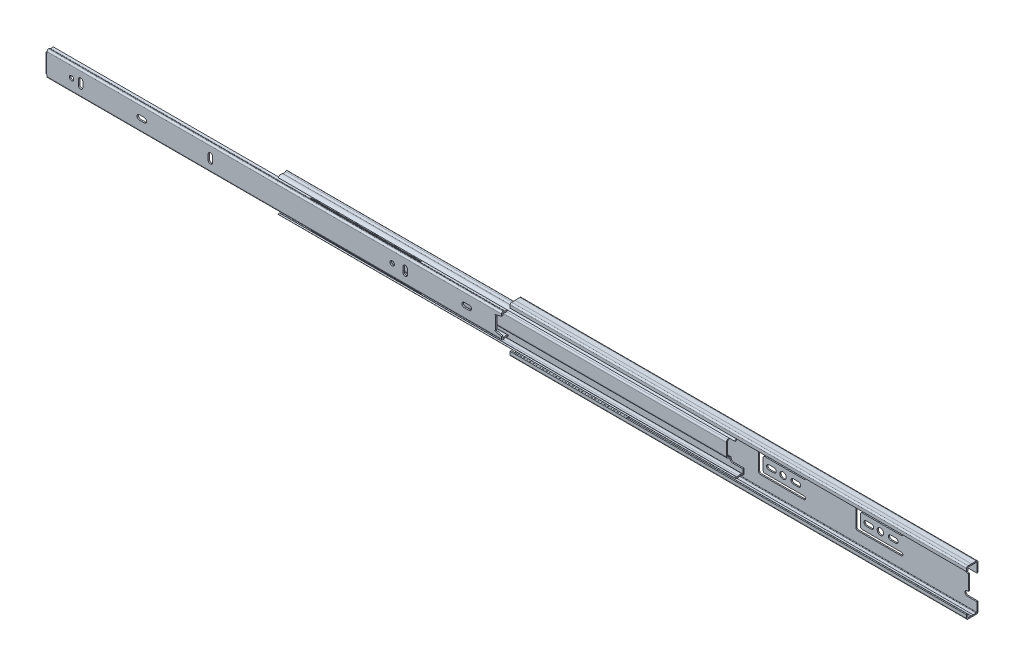
SolidWorks part; units mm, degrees
ref_plane "Front" through (0, 0, 0) normal (0, 0, 1) x (1, 0, 0)
ref_plane "Top" through (0, 0, 0) normal (0, 1, 0) x (1, 0, 0)
ref_plane "Right" through (0, 0, 0) normal (1, 0, 0) x (0, 0, -1)
sketch "Sketch1" plane through (0, 0, 0) normal (1, 0, 0) x (0, 0, -1)
  line L1 (5.6388, 0) -> (-5.6388, 0) construction
  line L4 (-4.1393, 22.8203) -> (-0.7433, 22.6989)
  line L5 (-1.1312, 21.5182) -> (-4.1819, 21.6273)
  line L6 (-4.445, 18.415) -> (-5.6388, 18.415)
  line L7 (-4.445, 21.3734) -> (-4.445, 18.415)
  line L8 (-5.6388, 18.415) -> (-5.6388, 21.3734)
  line L9 (3.9237, 21.6269) -> (0.7619, 21.5441)
  line L10 (5.6388, 0) -> (5.6388, 21.1191)
  line L11 (4.445, 21.1191) -> (4.445, 0)
  line L12 (5.6388, 0) -> (4.445, 0)
  line L13 (-0.7433, 22.6989) -> (3.8925, 22.8203)
  arc A0 (-4.445, 21.3734) -> (-4.1819, 21.6273) centre (-4.191, 21.3734) cw
  arc A1 (-5.6388, 21.3734) -> (-4.1393, 22.8203) centre (-4.191, 21.3734) cw
  arc A3 (3.9237, 21.6269) -> (4.445, 21.1191) centre (3.937, 21.1191) cw
  arc A4 (3.8925, 22.8203) -> (5.6388, 21.1191) centre (3.937, 21.1191) cw
  arc A5 (-1.1312, 21.5182) -> (0.7619, 21.5441) centre (-0.1524, 19.1744) cw
  dimension "D2" = 19.1744
  dimension "D7" = 0.254
  dimension "D8" = 0.508
  dimension "D6" = 2.54
  dimension "D9" = 1.1938
  dimension "D10" = 88.5
  dimension "D1" = 11.2776
  dimension "D3" = 5.7912
  dimension "D4" = 36.83
  dimension "D5" = 1.1938
  dimension "D11" = 87.953
  dimension "D12" = 45.6406
extrude "Extrude1" add sketch "Sketch1" along normal mid plane 450.088
ref_plane "Travel / 2" through (-453.644, 0, 0) normal (-1, 0, 0) x (0, 0, 1)
sketch "Sketch2" plane through (-453.644, 0, 0) normal (-1, 0, 0) x (0, 0, 1)
  line L0 (0.0254, 6.1159) -> (0.0254, 0)
  line L2 (-5.6388, 0) -> (5.6388, 0) construction
  line L3 (5.6388, 21.3734) -> (5.6388, 18.415) construction
  line L7 (-4.445, 21.1191) -> (-4.445, 0) construction
  line L8 (-5.6388, 0) -> (-5.6388, 21.1191) construction
  line L13 (-3.5306, 16.3766) -> (-3.5306, 9.5217)
  line L46 (-2.3867, 7.7262) -> (-0.4146, 6.8065)
  arc A0 (0.0254, 6.1159) -> (-0.4146, 6.8065) centre (-0.7366, 6.1159) ccw
  arc A1 (-1.5056, 17.2916) -> (1.2415, 16.9143) centre (0.1524, 19.1744) ccw
  arc A4 (1.1312, 21.5182) -> (-0.7619, 21.5441) centre (0.1524, 19.1744) ccw construction
  arc A19 (-3.5306, 9.5217) -> (-2.3867, 7.7262) centre (-1.5494, 9.5217) ccw
  arc A25 (-1.5056, 17.2916) -> (-3.5306, 16.3766) centre (-2.3114, 16.3766) ccw
  arc A51 (5.7404, 15.6277) -> (1.2415, 16.9143) centre (2.7686, 13.7451) ccw
  dimension "D2" = 8.4074
  dimension "D3" = 27.4903
  dimension "D6" = 1.9812
  dimension "D8" = 12.2319
  dimension "D10" = 2.5088
  dimension "D11" = 1.2192
  dimension "D4" = 0.762
  dimension "D5" = 4.4704
  dimension "D7" = 115
  dimension "D9" = 19.0435
  dimension "D13" = 11.3792
extrude "Middle Member" add sketch "Sketch2" against normal blind 450.088 separate body thin thin type one direction reverse wall 1.2192
ref_plane "Travel" through (-682.244, 0, 0) normal (-1, 0, 0) x (0, 0, 1)
sketch "Sketch3" plane through (-682.244, 0, 0) normal (-1, 0, 0) x (0, 0, 1)
  line L0 (1.2446, 0) -> (0.0254, 0) construction
  line L1 (-5.6388, 0) -> (-5.6388, 21.1191) construction
  line L56 (7.0612, 0) -> (7.0612, 10.6235)
  line L93 (5.5372, 12.1475) -> (5.1643, 12.1475)
  arc A0 (1.2082, 11.9072) -> (4.2365, 11.8325) centre (2.7686, 13.7451) ccw
  arc A29 (7.0612, 10.6235) -> (5.5372, 12.1475) centre (5.5372, 10.6235) ccw
  arc A53 (5.1643, 12.1475) -> (4.2365, 11.8325) centre (5.1643, 10.6235) ccw
  dimension "D1" = 1.524
  dimension "D4" = 1.524
  dimension "D5" = 2.411
  dimension "D2" = 12.7
  dimension "D3" = 12.1475
  dimension "D6" = 5.853
extrude "Drawer Member" add sketch "Sketch3" against normal blind 450.088 thin thin type one direction wall 1.397
sketch "Sketch6" plane through (0, 0, 7.0612) normal (0, 0, 1) x (1, 0, 0)
  line L1 (-682.244, 0) -> (-680.339, 0)
  line L2 (-682.244, 0) -> (-682.244, 12.1475)
  line L3 (-682.244, 12.1475) -> (-680.339, 12.1475)
  line L4 (-680.339, 0) -> (-680.339, 12.1475)
  line L5 (-232.156, 12.1475) -> (-682.244, 12.1475) construction
  line L7 (-682.244, 10.6235) -> (-682.244, 0) construction
  line L8 (-232.156, 0) -> (-682.244, 0) construction
  dimension "D1" = 1.905
extrude "Cut-Extrude1" cut sketch "Sketch6" against normal through all
sketch "Sketch7" plane through (0, 0, 0) normal (0, -1, 0) x (1, 0, 0)
  line L0 (-680.339, 7.0612) -> (-680.593, 7.0612)
  line L1 (-682.244, 5.4102) -> (-682.244, 0.3041)
  line L2 (-682.244, 0.3041) -> (-680.847, 0.3041)
  line L3 (-680.847, 0.3041) -> (-680.847, 5.4102)
  line L4 (-680.593, 5.6642) -> (-680.339, 5.6642)
  line L5 (-232.156, 5.6642) -> (-680.339, 5.6642) construction
  line L6 (-680.339, 7.0612) -> (-680.339, 5.6642)
  line L7 (-232.156, 0.3041) -> (-680.339, 0.3041) construction
  line L9 (-680.339, 5.087) -> (-680.339, 0.3041) construction
  arc A0 (-680.593, 5.6642) -> (-680.847, 5.4102) centre (-680.593, 5.4102) ccw
  arc A1 (-680.593, 7.0612) -> (-682.244, 5.4102) centre (-680.593, 5.4102) ccw
  dimension "D1" = 0.254
  dimension "D2" = 1.905
extrude "Extrude4" add sketch "Sketch7" against normal blind 8.89
sketch "Sketch8" plane through (0, 0, -4.445) normal (0, 0, 1) x (1, 0, 0)
  line L0 (215.4055, 7.6456) -> (216.8398, 7.493)
  line L1 (225.044, 12.2048) -> (215.6474, 12.2048)
  line L2 (216.8398, 7.493) -> (216.8398, 0)
  line L3 (225.044, 0) -> (-225.044, 0) construction
  line L4 (225.044, 21.1191) -> (225.044, 0) construction
  line L5 (225.044, 12.2048) -> (225.044, 0)
  line L6 (225.044, 0) -> (216.8398, 0)
  arc A0 (215.6474, 12.2048) -> (215.4055, 7.6456) centre (215.6474, 9.9188) ccw
  dimension "D3" = 9.9188
  dimension "D1" = 12.2048
  dimension "D2" = 8.2042
  dimension "D4" = 9.3966
  dimension "D5" = 7.493
extrude "Cut-Extrude2" cut sketch "Sketch8" against normal up to next (1.1938 mm away)
sketch "Sketch11" plane through (0, 0, 7.0612) normal (0, 0, 1) x (1, 0, 0)
  line L0 (-237.871, 5.9678) -> (-237.871, 0)
  line L8 (-232.156, 8.5893) -> (-238.0153, 7.2212)
  line L11 (-237.871, 0) -> (-232.156, 0)
  line L12 (-232.156, 0) -> (-232.156, 8.5893)
  arc A1 (-238.0153, 7.2212) -> (-237.871, 5.9678) centre (-237.8709, 6.6028) ccw
  dimension "D3" = 0.635
  dimension "D1" = 5.715
  dimension "D2" = 8.5893
  dimension "D4" = 5.9678
  dimension "D5" = 103.143
extrude "Cut-Extrude3" cut sketch "Sketch11" against normal up to next (1.397 mm away)
sketch "Sketch12" plane through (0, 0, 1.2446) normal (0, 0, 1) x (1, 0, 0)
  line L0 (-3.556, 12.065) -> (-13.716, 12.065)
  line L1 (-3.556, 16.3766) -> (-3.556, 9.5217) construction
  line L2 (-16.256, 9.525) -> (-16.256, 0)
  line L3 (-3.556, 0) -> (-453.644, 0) construction
  line L4 (-16.256, 0) -> (-3.556, 0)
  line L5 (-3.556, 0) -> (-3.556, 12.065)
  arc A0 (-13.716, 12.065) -> (-16.256, 9.525) centre (-13.716, 9.525) ccw
  point P11 (-16.256, 12.065)
  dimension "D3" = 2.54
  dimension "D1" = 12.7
  dimension "D2" = 12.065
extrude "Cut-Extrude4" cut sketch "Sketch12" against normal through all
sketch "Sketch13" plane through (0, 0, -4.445) normal (0, 0, 1) x (1, 0, 0)
  line L0 (-156.6557, 7.112) -> (-181.4842, 7.112)
  line L1 (216.8398, 0) -> (-225.044, 0) construction
  line L2 (-164.7456, 0) -> (-164.7456, 4.2392) construction
  line L3 (-207.5827, 10.287) -> (-156.6557, 10.287)
  line L4 (-225.044, 21.1191) -> (-225.044, 0) construction
  line L5 (-185.2942, 7.112) -> (-207.5827, 7.112)
  line L6 (-184.5322, 0) -> (-184.5322, 6.35)
  line L7 (-182.2462, 6.35) -> (-182.2462, 0)
  line L8 (-162.2691, 2.286) -> (-167.2221, 2.286)
  line L13 (-201.3216, 0) -> (-196.7496, 0)
  line L14 (-193.219, 0) -> (-186.869, 0)
  line L15 (-184.5322, 0) -> (-182.2462, 0)
  line L16 (-179.7316, 0) -> (-175.1596, 0)
  line L17 (-169.5081, 0) -> (-159.9831, 0)
  arc A1 (-207.5827, 10.287) -> (-207.5827, 7.112) centre (-207.5827, 8.6995) ccw
  arc A2 (-184.5322, 6.35) -> (-185.2942, 7.112) centre (-185.2942, 6.35) ccw
  arc A4 (-181.4842, 7.112) -> (-182.2462, 6.35) centre (-181.4842, 6.35) ccw
  arc A7 (-156.6557, 7.112) -> (-156.6557, 10.287) centre (-156.6557, 8.6995) ccw
  arc A8 (-186.869, 0) -> (-193.219, 0) centre (-190.044, 0) ccw
  arc A9 (-196.7496, 0) -> (-201.3216, 0) centre (-199.0356, 0) ccw
  arc A10 (-175.1596, 0) -> (-179.7316, 0) centre (-177.4456, 0) ccw
  arc A11 (-159.9831, 0) -> (-162.2691, 2.286) centre (-162.2691, 0) ccw
  arc A12 (-167.2221, 2.286) -> (-169.5081, 0) centre (-167.2221, 0) ccw
  dimension "D3" = 2.286
  dimension "D4" = 3.175
  dimension "D7" = 8.9916
  dimension "D8" = 21.59
  dimension "D9" = 34.29
  dimension "D10" = 0.762
  dimension "D11" = 17.5387
  dimension "D12" = 9.525
  dimension "D13" = 5.5118
  dimension "D14" = 35
  dimension "D1" = 3.175
  dimension "D2" = 50.927
  dimension "D5" = 2.286
  dimension "D6" = 10.287
extrude "Cut-Extrude5" cut sketch "Sketch13" against normal up to next (1.1938 mm away)
sketch "Sketch32" plane through (0, 0, -5.6388) normal (0, 0, -1) x (-1, 0, 0)
  line L0 (44.5815, 0) -> (54.1065, 0)
  line L1 (58.869, 0) -> (65.219, 0)
  line L2 (68.7115, 0) -> (78.2365, 0)
  line L3 (81.602, 0) -> (86.174, 0)
  line L4 (-216.8398, 0) -> (159.9831, 0) construction
  line L5 (207.5827, 10.287) -> (156.6557, 10.287) construction
  line L6 (156.6557, 7.112) -> (181.4842, 7.112) construction
  line L7 (73.474, 2.286) -> (73.474, -3.4269) construction
  line L8 (49.344, 2.286) -> (49.344, -3.4269) construction
  line L14 (41.4065, 10.287) -> (84.65, 10.287)
  line L15 (80.078, 7.112) -> (41.4065, 7.112)
  line L17 (86.174, 8.763) -> (86.174, 0)
  line L18 (81.602, 0) -> (81.602, 5.588)
  line L23 (46.8675, 2.286) -> (51.8205, 2.286)
  line L25 (70.9975, 2.286) -> (75.9505, 2.286)
  arc A0 (193.219, 0) -> (186.869, 0) centre (190.044, 0) ccw construction
  arc A13 (86.174, 8.763) -> (84.65, 10.287) centre (84.65, 8.763) ccw
  arc A14 (81.602, 5.588) -> (80.078, 7.112) centre (80.078, 5.588) ccw
  arc A17 (41.4065, 10.287) -> (41.4065, 7.112) centre (41.4065, 8.6995) ccw
  arc A20 (54.1065, 0) -> (51.8205, 2.286) centre (51.8205, 0) ccw
  arc A21 (46.8675, 2.286) -> (44.5815, 0) centre (46.8675, 0) ccw
  arc A22 (65.219, 0) -> (58.869, 0) centre (62.044, 0) ccw
  arc A24 (78.2365, 0) -> (75.9505, 2.286) centre (75.9505, 0) ccw
  arc A25 (70.9975, 2.286) -> (68.7115, 0) centre (70.9975, 0) ccw
  dimension "D2" = 1.524
  dimension "D3" = 3.175
  dimension "D4" = 9.525
  dimension "D5" = 2.286
  dimension "D6" = 11.43
  dimension "D7" = 12.7
  dimension "D8" = 24.13
  dimension "D9" = 20.6375
  dimension "D10" = 128
  dimension "D1" = 4.572
extrude "Cut-Extrude14" cut sketch "Sketch32" against normal up to next (1.1938 mm away)
sketch "Sketch33" plane through (83.6094, 0.8125, -5.6388) normal (0, 0, -1) x (-1, 0, 0)
  line L0 (32.1909, -0.8125) -> (41.7159, -0.8125)
  line L1 (46.4784, -0.8125) -> (52.8284, -0.8125)
  line L2 (56.3209, -0.8125) -> (65.8459, -0.8125)
  line L3 (69.2114, -0.8125) -> (73.7834, -0.8125)
  line L7 (61.0834, 1.4735) -> (61.0834, -4.2394) construction
  line L8 (36.9534, 1.4735) -> (36.9534, -3.4269) construction
  line L9 (-133.2304, -0.8125) -> (128.1909, -0.8125) construction
  line L10 (168.2594, 9.4745) -> (125.0159, 9.4745) construction
  line L11 (125.0159, 6.2995) -> (163.6874, 6.2995) construction
  line L14 (29.0159, 9.4745) -> (72.2594, 9.4745)
  line L15 (67.6874, 6.2995) -> (29.0159, 6.2995)
  line L17 (73.7834, 7.9505) -> (73.7834, -0.8125)
  line L18 (69.2114, -0.8125) -> (69.2114, 4.7755)
  line L23 (34.4769, 1.4735) -> (39.4299, 1.4735)
  line L25 (58.6069, 1.4735) -> (63.5599, 1.4735)
  arc A1 (276.8284, -0.8125) -> (270.4784, -0.8125) centre (273.6534, -0.8125) ccw construction
  arc A13 (73.7834, 7.9505) -> (72.2594, 9.4745) centre (72.2594, 7.9505) ccw
  arc A14 (69.2114, 4.7755) -> (67.6874, 6.2995) centre (67.6874, 4.7755) ccw
  arc A17 (29.0159, 9.4745) -> (29.0159, 6.2995) centre (29.0159, 7.887) ccw
  arc A20 (41.7159, -0.8125) -> (39.4299, 1.4735) centre (39.4299, -0.8125) ccw
  arc A21 (34.4769, 1.4735) -> (32.1909, -0.8125) centre (34.4769, -0.8125) ccw
  arc A22 (52.8284, -0.8125) -> (46.4784, -0.8125) centre (49.6534, -0.8125) ccw
  arc A24 (65.8459, -0.8125) -> (63.5599, 1.4735) centre (63.5599, -0.8125) ccw
  arc A25 (58.6069, 1.4735) -> (56.3209, -0.8125) centre (58.6069, -0.8125) ccw
  dimension "D2" = 1.524
  dimension "D3" = 3.175
  dimension "D4" = 9.525
  dimension "D5" = 2.286
  dimension "D6" = 11.43
  dimension "D7" = 12.7
  dimension "D8" = 24.13
  dimension "D9" = 20.6375
  dimension "D10" = 224
  dimension "D1" = 4.572
extrude "Cut-Extrude6" cut sketch "Sketch33" against normal up to next (1.1938 mm away)
sketch "Sketch34" plane through (169.8236, 1.4527, -5.6388) normal (0, 0, -1) x (-1, 0, 0)
  line L0 (22.3651, -1.4527) -> (31.8901, -1.4527)
  line L1 (36.6526, -1.4527) -> (43.0026, -1.4527)
  line L2 (46.4951, -1.4527) -> (56.0201, -1.4527)
  line L3 (59.3856, -1.4527) -> (63.9576, -1.4527)
  line L4 (-47.0162, -1.4527) -> (118.4051, -1.4527) construction
  line L7 (51.2576, 0.8333) -> (51.2576, -4.8796) construction
  line L8 (27.1276, 0.8333) -> (27.1276, -4.0671) construction
  line L9 (254.4736, 8.8343) -> (211.2301, 8.8343) construction
  line L10 (211.2301, 5.6593) -> (249.9016, 5.6593) construction
  line L14 (19.1901, 8.8343) -> (62.4336, 8.8343)
  line L15 (57.8616, 5.6593) -> (19.1901, 5.6593)
  line L17 (63.9576, 7.3103) -> (63.9576, -1.4527)
  line L18 (59.3856, -1.4527) -> (59.3856, 4.1353)
  line L23 (24.6511, 0.8333) -> (29.6041, 0.8333)
  line L25 (48.7811, 0.8333) -> (53.7341, 0.8333)
  arc A0 (363.0426, -1.4527) -> (356.6926, -1.4527) centre (359.8676, -1.4527) ccw construction
  arc A13 (63.9576, 7.3103) -> (62.4336, 8.8343) centre (62.4336, 7.3103) ccw
  arc A14 (59.3856, 4.1353) -> (57.8616, 5.6593) centre (57.8616, 4.1353) ccw
  arc A17 (19.1901, 8.8343) -> (19.1901, 5.6593) centre (19.1901, 7.2468) ccw
  arc A20 (31.8901, -1.4527) -> (29.6041, 0.8333) centre (29.6041, -1.4527) ccw
  arc A21 (24.6511, 0.8333) -> (22.3651, -1.4527) centre (24.6511, -1.4527) ccw
  arc A22 (43.0026, -1.4527) -> (36.6526, -1.4527) centre (39.8276, -1.4527) ccw
  arc A24 (56.0201, -1.4527) -> (53.7341, 0.8333) centre (53.7341, -1.4527) ccw
  arc A25 (48.7811, 0.8333) -> (46.4951, -1.4527) centre (48.7811, -1.4527) ccw
  dimension "D2" = 1.524
  dimension "D3" = 3.175
  dimension "D4" = 9.525
  dimension "D5" = 2.286
  dimension "D6" = 11.43
  dimension "D7" = 12.7
  dimension "D8" = 24.13
  dimension "D9" = 20.6375
  dimension "D10" = 320.04
  dimension "D1" = 4.572
extrude "Cut E" cut sketch "Sketch34" against normal up to next (1.1938 mm away)
sketch "Sketch24" plane through (0, 0, 7.0612) normal (0, 0, 1) x (1, 0, 0)
  line L0 (-237.871, 0) -> (-680.593, 0) construction
  line L1 (-647.192, 4.826) -> (-647.192, 0) construction
  line L2 (-649.3764, 2.6416) -> (-649.3764, 0)
  line L3 (-649.3764, 0) -> (-645.0076, 0)
  line L4 (-645.0076, 0) -> (-645.0076, 2.6416)
  line L5 (-591.5025, 0) -> (-581.9775, 0)
  line L6 (-589.2165, 2.286) -> (-584.2635, 2.286)
  line L8 (-521.3764, 2.6416) -> (-521.3764, 0)
  line L9 (-521.3764, 0) -> (-517.0076, 0)
  line L10 (-517.0076, 0) -> (-517.0076, 2.6416)
  line L11 (-682.244, 8.89) -> (-682.244, 0) construction
  line L12 (-586.74, 2.286) -> (-586.74, 0) construction
  circle A0 centre (-656.082, 0) radius 2.1844
  arc A1 (-649.3764, 2.6416) -> (-645.0076, 2.6416) centre (-647.192, 2.6416) cw
  arc A2 (-591.5025, 0) -> (-589.2165, 2.286) centre (-589.2165, 0) cw
  arc A3 (-584.2635, 2.286) -> (-581.9775, 0) centre (-584.2635, 0) cw
  arc A4 (-521.3764, 2.6416) -> (-517.0076, 2.6416) centre (-519.192, 2.6416) cw
  dimension "D1" = 4.3688
  dimension "D4" = 8.89
  dimension "D5" = 2.286
  dimension "D7" = 60.452
  dimension "D8" = 128
  dimension "D2" = 35.052
  dimension "D3" = 4.826
  dimension "D6" = 9.525
extrude "Cut-Extrude13" cut sketch "Sketch24" against normal up to next (1.397 mm away)
sketch "Sketch25" plane through (0, 0, 7.0612) normal (0, 0, 1) x (1, 0, 0)
  line L1 (-237.871, 0) -> (-517.0076, 0) construction
  line L5 (-261.6835, 0) -> (-271.2085, 0)
  line L6 (-584.2635, 2.286) -> (-589.2165, 2.286) construction
  line L7 (-268.9225, 2.286) -> (-263.9695, 2.286)
  line L8 (-266.446, 0) -> (-266.446, 2.286) construction
  arc A1 (-645.0076, 2.6416) -> (-649.3764, 2.6416) centre (-647.192, 2.6416) ccw construction
  arc A3 (-268.9225, 2.286) -> (-271.2085, 0) centre (-268.9225, 0) ccw
  arc A4 (-263.9695, 2.286) -> (-261.6835, 0) centre (-263.9695, 0) cw
  arc A5 (-581.9775, 0) -> (-584.2635, 2.286) centre (-584.2635, 0) ccw construction
  dimension "D1" = 380.746
extrude "Cut D" cut sketch "Sketch25" against normal up to next (1.397 mm away)
sketch "Sketch36" plane through (0, 0, 7.0612) normal (0, 0, 1) x (1, 0, 0)
  line L0 (-329.3364, 0) -> (-324.9676, 0)
  line L1 (-324.9676, 0) -> (-324.9676, 2.6416)
  line L2 (-329.3364, 2.6416) -> (-329.3364, 0)
  line L4 (-271.2085, 0) -> (-517.0076, 0) construction
  line L5 (-645.0076, 0) -> (-645.0076, 2.6416) construction
  arc A0 (-324.9676, 2.6416) -> (-329.3364, 2.6416) centre (-327.152, 2.6416) ccw
  circle A1 centre (-339.852, 0) radius 2.1844
  arc A5 (-645.0076, 2.6416) -> (-649.3764, 2.6416) centre (-647.192, 2.6416) ccw construction
  dimension "D1" = 4.3688
  dimension "D2" = 320.04
  dimension "D3" = 12.7
extrude "Cut B" cut sketch "Sketch36" against normal up to next (1.397 mm away)
sketch "Sketch38" plane through (0, 0, 7.0612) normal (0, 0, 1) x (1, 0, 0)
  line L0 (-425.3764, 0) -> (-425.3764, 2.6416)
  line L1 (-342.0364, 0) -> (-517.0076, 0) construction
  line L2 (-421.0076, 2.6416) -> (-421.0076, 0)
  line L3 (-421.0076, 0) -> (-425.3764, 0)
  line L4 (-645.0076, 0) -> (-645.0076, 2.6416) construction
  line L5 (-416.461, 0) -> (-408.587, 0)
  line L6 (-416.461, 0) -> (-416.461, 2.3749)
  line L7 (-416.461, 2.3749) -> (-408.587, 2.3749)
  line L8 (-408.587, 0) -> (-408.587, 2.3749)
  line L9 (-423.192, 7.182) -> (-423.192, -4.0911) construction
  line L10 (-429.923, 0) -> (-437.797, 0)
  line L11 (-429.923, 0) -> (-429.923, 2.3749)
  line L12 (-429.923, 2.3749) -> (-437.797, 2.3749)
  line L13 (-437.797, 0) -> (-437.797, 2.3749)
  line L14 (-412.524, 2.3749) -> (-412.524, -3.2385) construction
  arc A0 (-425.3764, 2.6416) -> (-421.0076, 2.6416) centre (-423.192, 2.6416) cw
  arc A1 (-645.0076, 2.6416) -> (-649.3764, 2.6416) centre (-647.192, 2.6416) ccw construction
  dimension "D4" = 224
  dimension "D1" = 7.874
  dimension "D2" = 2.3749
  dimension "D3" = 10.668
extrude "Cut A" [suppressed] cut sketch "Sketch38" against normal up to next
ref_plane "Plane3" through (-212.344, 0, 0) normal (-1, 0, 0) x (0, 0, 1)
sketch "Sketch27" plane through (-212.344, 0, 0) normal (-1, 0, 0) x (0, 0, 1)
  line L0 (0.1524, 21.6832) -> (0.1524, 16.6656)
  line L1 (0.1524, 23.635) -> (0.1524, 15.2838) construction
  arc A0 (0.1524, 16.6656) -> (0.1524, 21.6832) centre (0.1524, 19.1744) ccw
  arc A1 (-1.5056, 17.2916) -> (1.2415, 16.9143) centre (0.1524, 19.1744) ccw construction
revolve "Revolve1" add sketch "Sketch27" angle 360 about L1
pattern_linear "LPattern1" count 6 spacing 19.05 along (1, 0, 0) of bodies 128
sketch "Sketch28" plane through (-212.344, 0, 0) normal (-1, 0, 0) x (0, 0, 1)
  line L0 (2.6612, 19.1744) -> (-2.3564, 19.1744) construction
  line L1 (3.9624, 18.7934) -> (-3.6576, 18.7934)
  line L2 (3.9624, 18.7934) -> (3.9624, 19.5554)
  line L3 (3.9624, 19.5554) -> (-3.6576, 19.5554)
  line L4 (-3.6576, 18.7934) -> (-3.6576, 19.5554)
  line L5 (0.1524, 20.5465) -> (0.1524, 17.804) construction
  circle A1 centre (0.1524, 19.1744) radius 2.5088 construction
  point P8 (0.1524, 19.1744)
  dimension "D1" = 7.62
  dimension "D2" = 0.762
extrude "Extrude7" add sketch "Sketch28" along normal blind 6.35 and the other way blind 101.6
ref_plane "Plane4" through (-415.544, 0, 0) normal (-1, 0, 0) x (0, 0, 1)
sketch "Sketch29" plane through (-415.544, 0, 0) normal (-1, 0, 0) x (0, 0, 1)
  line L0 (2.7686, 16.0438) -> (2.7686, 11.4464)
  line L1 (2.7686, 16.6801) -> (2.7686, 10.2973) construction
  arc A0 (2.7686, 11.4464) -> (2.7686, 16.0438) centre (2.7686, 13.7451) ccw
  arc A1 (4.7105, 14.9753) -> (1.7707, 15.816) centre (2.7686, 13.7451) ccw construction
revolve "Revolve2" add sketch "Sketch29" angle 360 about L1
pattern_linear "LPattern2" count 6 spacing 19.05 along (1, 0, 0) of bodies 135
sketch "Sketch30" plane through (-415.544, 0, 0) normal (-1, 0, 0) x (0, 0, 1)
  line L0 (0.4699, 13.7451) -> (5.0673, 13.7451) construction
  line L1 (3.9624, 18.7934) -> (3.9624, 19.5554) construction
  line L2 (0.2286, 14.1261) -> (5.3086, 14.1261)
  line L3 (0.2286, 14.1261) -> (0.2286, 13.3641)
  line L4 (0.2286, 13.3641) -> (5.3086, 13.3641)
  line L5 (5.3086, 14.1261) -> (5.3086, 13.3641)
  line L7 (2.7686, 14.2437) -> (2.7686, 12.7853) construction
  circle A0 centre (2.7686, 13.7451) radius 2.2987 construction
  point P4 (2.7686, 13.7451)
  dimension "D1" = 5.08
extrude "Extrude8" add sketch "Sketch30" along normal blind 6.35 and the other way blind 101.6
mirror "Mirror3" about plane through (0, 0, 0) normal (0, 1, 0) of bodies 168 119 164 117 124 126 127 159
mirror "Mirror5" about plane through (0, 0, 0) normal (0, 1, 0) of bodies 141 134
